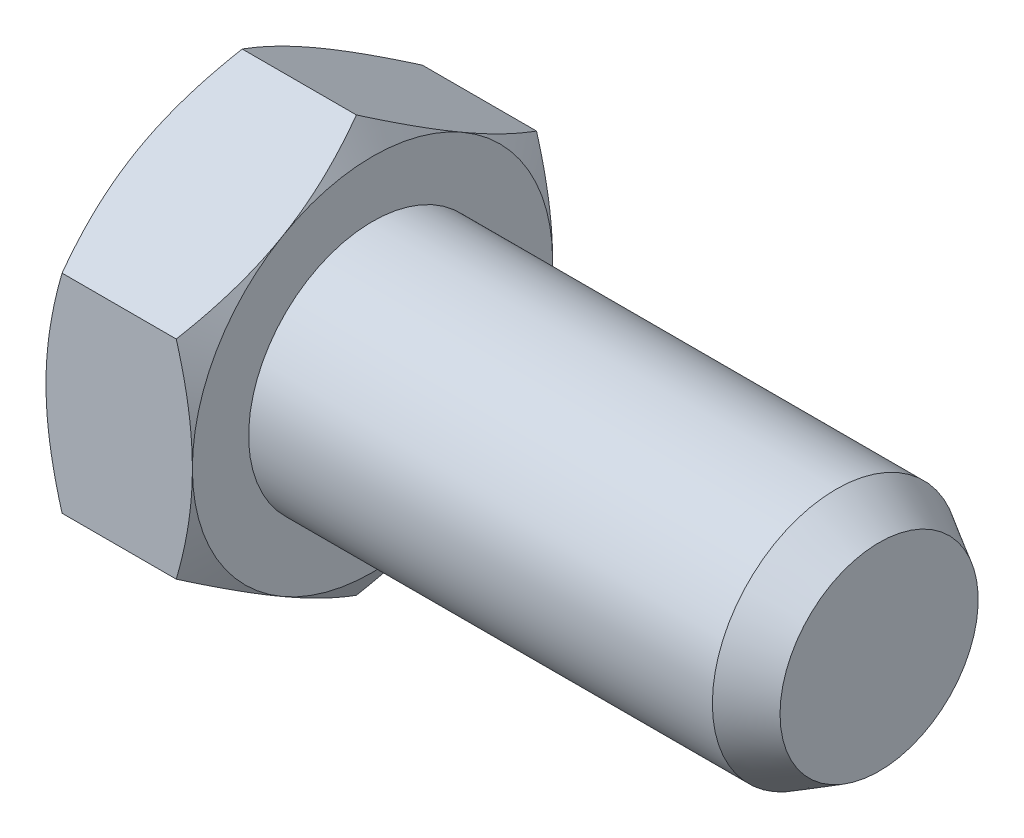
SolidWorks part; units mm, degrees
ref_plane "Front" through (0, 0, 0) normal (0, 0, 1) x (1, 0, 0)
ref_plane "Top" through (0, 0, 0) normal (0, 1, 0) x (1, 0, 0)
ref_plane "Right" through (0, 0, 0) normal (1, 0, 0) x (0, 0, -1)
sketch "Sketch1" plane through (0, 0, 0) normal (0, 0, 1) x (1, 0, 0)
  line L0 (0, 0) -> (0, 1.4)
  line L1 (0, 1.4) -> (1.3, 1.4)
  line L2 (1.3, 1.4) -> (1.3, 1.1)
  line L4 (1.3, 1.1) -> (5.8, 1.1)
  line L5 (5.8, 1.1) -> (5.8, 0)
  line L6 (5.8, 0) -> (0, 0)
  line L7 (13.1079, 0) -> (-2.2203, 0) construction
revolve "Revolve1" add sketch "Sketch1" angle 360 about L7
cosmetic thread "ThreadCosmetic" [suppressed] parameters "D2"=1.5
sketch "Sketch2" plane through (0, 0, 0) normal (-1, 0, 0) x (0, 0, 1)
  line L1 (1.6, -0.9238) -> (1.6, 0.9238)
  line L2 (1.6, 0.9238) -> (0, 1.8475)
  line L3 (0, 1.8475) -> (-1.6, 0.9238)
  line L4 (-1.6, 0.9238) -> (-1.6, -0.9238)
  line L5 (-1.6, -0.9238) -> (0, -1.8475)
  line L6 (0, -1.8475) -> (1.6, -0.9238)
  circle A0 centre (0, 0) radius 1.6 construction
extrude "Extrude1" add sketch "Sketch2" against normal blind 1.3
sketch "Sketch3" plane through (0, 0, 0) normal (0, 1, 0) x (1, 0, 0)
  line L0 (-0.9238, 0) -> (0.65, 2.7258)
  line L1 (0.65, 2.7258) -> (1.3, 1.6)
  line L2 (0, 0) -> (-2.2444, 0) construction
  line L4 (1.3, 1.6) -> (1.3, 3.2258)
  line L5 (1.3, 3.2258) -> (-1.0238, 3.2258)
  line L6 (-0.9238, 0) -> (-1.0238, 0)
  line L7 (-1.0238, 0) -> (-1.0238, 3.2258)
  dimension "D1" = 60
  dimension "D2" = 0.5
  dimension "D3" = 0.1
  dimension "D4" = 60
revolve "Cut-Revolve2" cut sketch "Sketch3" angle 360 about L2
sketch "Sketch4" plane through (0, 0, 0) normal (0, 0, 1) x (1, 0, 0)
  line L0 (0, 0) -> (1.9538, 0) construction
  line L1 (-0.2, 0) -> (-0.2, 1.28)
  line L2 (-0.2, 1.28) -> (0.4, 1.28)
  line L3 (0.4, 1.28) -> (0.4, 0)
  line L4 (1.3, 1.4) -> (1.3, 1.1) construction
  line L5 (1.3, 1.4) -> (1.3, 1.8049) construction
  line L6 (0.4, 0) -> (-0.2, 0)
  dimension "D1" = 0.2
  dimension "D2" = 2.56
revolve "Cut-Revolve3" cut sketch "Sketch4" angle 360 about L0
chamfer "Chamfer1" distance 0.22 angle 60 1 edges at (5.8, 0, -1.1) first distance on face at (5.8, 0, -1.1)
sketch "Sketch6" plane through (0, 0, 0) normal (0, 0, 1) x (1, 0, 0)
  line L0 (1.627, 0.75) -> (1.5502, 0.75)
  line L1 (1.5502, 0.75) -> (1.3481, 1.1)
  line L2 (1.627, 0.75) -> (1.829, 1.1)
  line L3 (1.3481, 1.1) -> (1.3481, 1.35)
  line L4 (1.829, 1.1) -> (1.829, 1.35)
  line L5 (1.3481, 1.35) -> (1.829, 1.35)
  line L6 (1.5886, 0.75) -> (1.5886, 0) construction
  line L7 (0, 0) -> (7.3035, 0) construction
  dimension "D2" = 60
  dimension "D3" = 0.25
  dimension "minordia" = 1.5
  dimension "threadstart" = 1.5886
  dimension "D1" = 2.2
revolve "ThreadSchematic" [suppressed] cut sketch "Sketch6" angle 360 about L7
pattern_linear "ThdSchPat" [suppressed] count 10 spacing 0.4809 along (1, 0, 0) of bodies 139
sketch "Sketch5" plane through (0, 0, 0) normal (0, 0, 1) x (1, 0, 0)
  line L0 (5.8, -0.88) -> (5.8, 0.88) construction
  line L2 (5.8, -1.1) -> (5.8, 0) construction
  line L3 (3.8, -1.1) -> (4.3, -1.1) construction
  line L4 (0, 0) -> (6.648, 0) construction
  line L5 (5.8, 0) -> (4.3, -1.1)
  line L6 (5.8, 0) -> (6, 0)
  line L7 (6, 0) -> (6, -1.3)
  line L8 (6, -1.3) -> (4.3, -1.3)
  line L9 (4.3, -1.3) -> (4.3, -1.1)
  line L10 (4.3, -1.1) -> (5.8, -1.1) construction
  dimension "D1" = 0.2
  dimension "D2" = 0.5
  dimension "D3" = 0.2
  dimension "D4" = 2.2
revolve "EndCone" [suppressed] cut sketch "Sketch5" angle 360 about L4
equation "\"minordia@Sketch6\" = \"D2@ThreadCosmetic\""
equation "\"D1@Extrude1\" = \"k@Sketch1\""
equation "\"D2@Sketch4\" = \"s@Sketch2\" * 4 / 5"
equation "\"D1@Chamfer1\" = \"d@Sketch1\" / 10"
equation "\"D2@Sketch5\" = \"y@Sketch5\" / 4"
equation "\"threadstart@Sketch6\" = \"D1@Extrude1\"+(\"advance@Sketch6\"*0.6)"
equation "\"D1@ThdSchPat\" = int((\"l@Sketch1\"/\"advance@Sketch6\") + 0.999)"
equation "\"D3@ThdSchPat\" = \"advance@Sketch6\""
equation "\"D1@Sketch6\" = \"d@Sketch1\""
equation "\"D4@Sketch5\" = \"d@Sketch1\""
